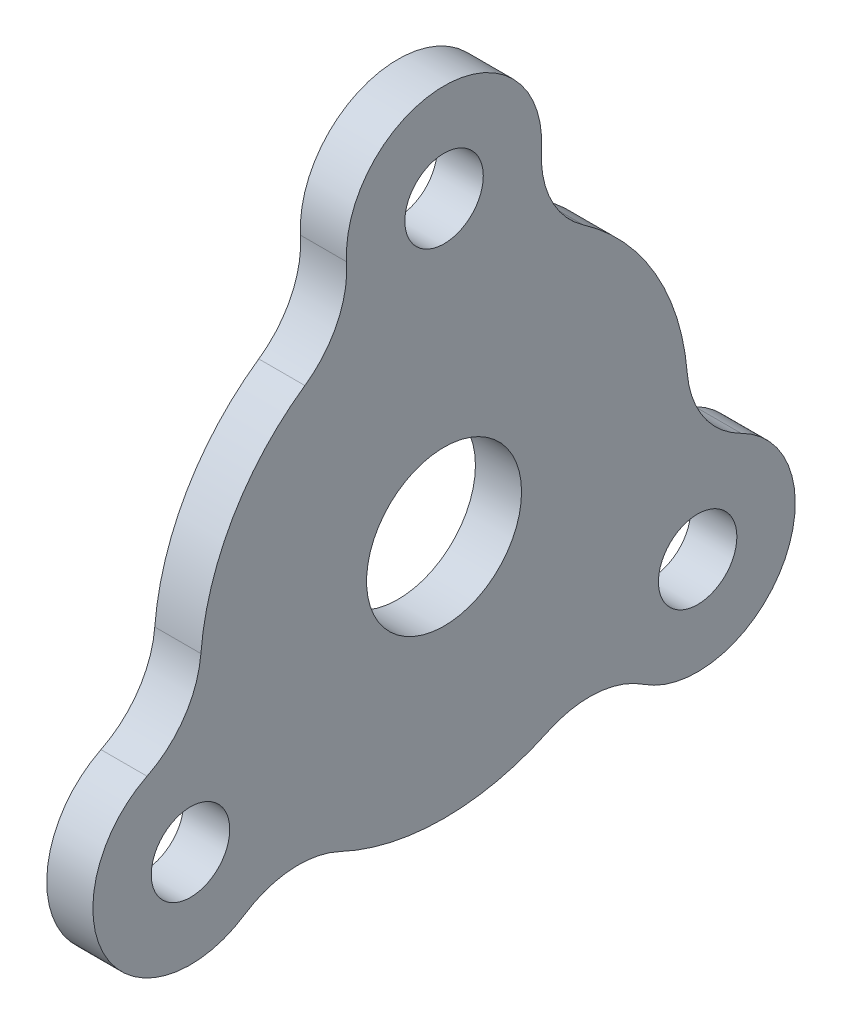
SolidWorks part; units mm, degrees
material "AR500"
ref_plane "Front Plane" through (0, 0, 0) normal (0, 0, 1) x (1, 0, 0)
ref_plane "Top Plane" through (0, 0, 0) normal (0, 1, 0) x (1, 0, 0)
ref_plane "Right Plane" through (0, 0, 0) normal (1, 0, 0) x (0, 0, -1)
sketch "Sketch1" plane through (0, 0, 0) normal (1, 0, 0) x (0, 0, -1)
  line L1 (0, 19.05) -> (-16.4978, -9.525) construction
  line L2 (-16.4978, -9.525) -> (16.4978, -9.525) construction
  line L3 (16.4978, -9.525) -> (0, 19.05) construction
  arc A1 (-9.0537, 13.0402) -> (-15.82, 1.3206) centre (0, 0) ccw
  circle A2 centre (0, 19.05) radius 2.5527
  circle A3 centre (-16.4978, -9.525) radius 2.5527
  circle A4 centre (16.4978, -9.525) radius 2.5527
  arc A6 (-15.82, 1.3206) -> (-19.3229, -3.8381) centre (-22.148, 1.8489) cw
  arc A7 (-19.3229, -3.8381) -> (-12.9853, -14.8151) centre (-16.4978, -9.525) ccw
  arc A8 (-12.9853, -14.8151) -> (-6.7663, -14.3608) centre (-9.4728, -20.1051) cw
  circle A9 centre (0, 0) radius 19.05 construction
  arc A10 (9.0537, 13.0402) -> (6.3376, 18.6531) centre (12.6752, 18.2563) cw
  arc A11 (6.3376, 18.6531) -> (-6.3376, 18.6531) centre (0, 19.05) ccw
  arc A12 (-6.3376, 18.6531) -> (-9.0537, 13.0402) centre (-12.6752, 18.2563) cw
  arc A13 (6.7663, -14.3608) -> (12.9853, -14.8151) centre (9.4728, -20.1051) cw
  arc A14 (12.9853, -14.8151) -> (19.3229, -3.8381) centre (16.4978, -9.525) ccw
  arc A15 (19.3229, -3.8381) -> (15.82, 1.3206) centre (22.148, 1.8489) cw
  circle A16 centre (0, 19.05) radius 2.0193 construction
  arc A17 (15.82, 1.3206) -> (9.0537, 13.0402) centre (0, 0) ccw
  arc A19 (-6.7663, -14.3608) -> (6.7663, -14.3608) centre (0, 0) ccw
  point P35 (0, 0)
  dimension "D4" = 5.1054
  dimension "D5" = 6.35
  dimension "D6" = 6.35
  dimension "D7" = 15.875
  dimension "D2" = 3
extrude "Boss-Extrude1" add sketch "Sketch1" along normal blind 3
sketch "Sketch5" plane through (3, 0, 0) normal (1, 0, 0) x (0, 0, -1)
  point P0 (0, 0)
hole_wizard "3/8 Clearance Hole1" positions "Sketch5" profile "Sketch6" hole size "3/8" standard "ANSI Inch" end condition through all
sketch "Sketch6" plane through (3, 0, 0) normal (0, 1, 0) x (0, 0, -1)
  line L0 (0, 0) -> (0, 3)
  line L1 (0, 3) -> (5.0419, 3)
  line L2 (5.0419, 3) -> (5.0419, 0)
  line L5 (5.0419, 0) -> (0, 0)
  line L11 (0, -6.35) -> (0, 107.95) construction
  dimension "Thru Hole Dia." = 10.0838
  dimension "Thru Hole Depth" = 3
